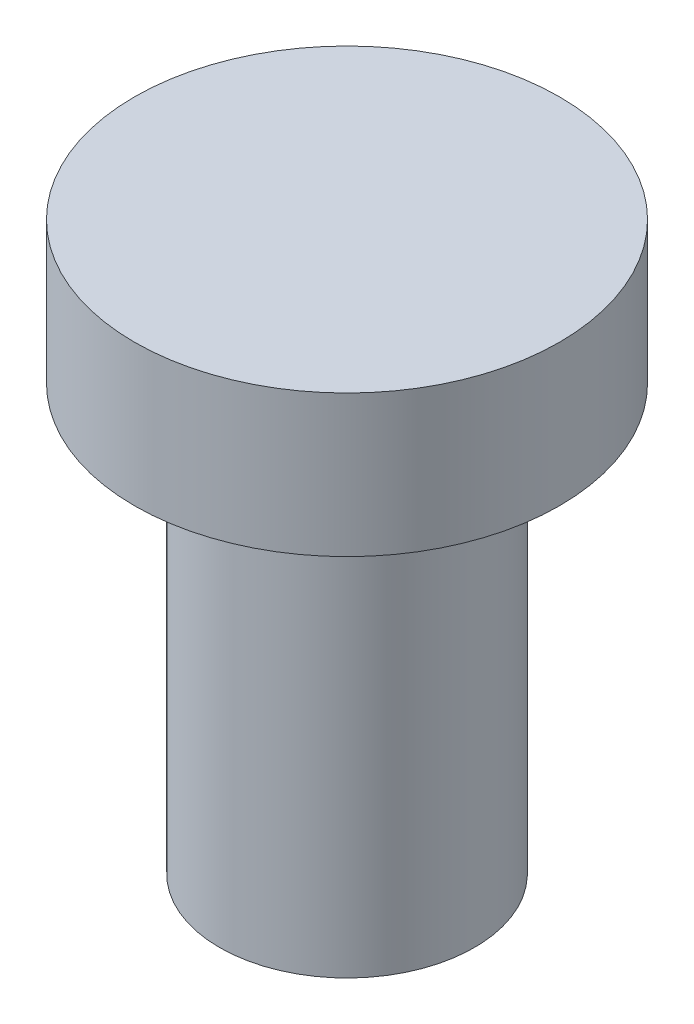
SolidWorks part; units mm, degrees
ref_plane "Front Plane" through (0, 0, 0) normal (0, 0, 1) x (1, 0, 0)
ref_plane "Top Plane" through (0, 0, 0) normal (0, 1, 0) x (1, 0, 0)
ref_plane "Right Plane" through (0, 0, 0) normal (1, 0, 0) x (0, 0, -1)
sketch "Sketch1" plane through (0, 0, 0) normal (0, 1, 0) x (1, 0, 0)
  circle A0 centre (0, 0) radius 1.8
  circle A1 centre (0, 0) radius 3
  dimension "D1" = 3.6
  dimension "D2" = 6
extrude "Boss-Extrude1" add sketch "Sketch1" against normal blind 6 contours A0 region at (0, 0, 0)
extrude "Boss-Extrude2" add sketch "Sketch1<3>" along normal blind 2 contours A0 | A1 A0 region at (0, 0, 0) region at (-2.9151, 0, 0)
sketch "Sketch1<3>" plane through (0, 0, 0) normal (0, 1, 0) x (1, 0, 0) same geometry as "Sketch1"
